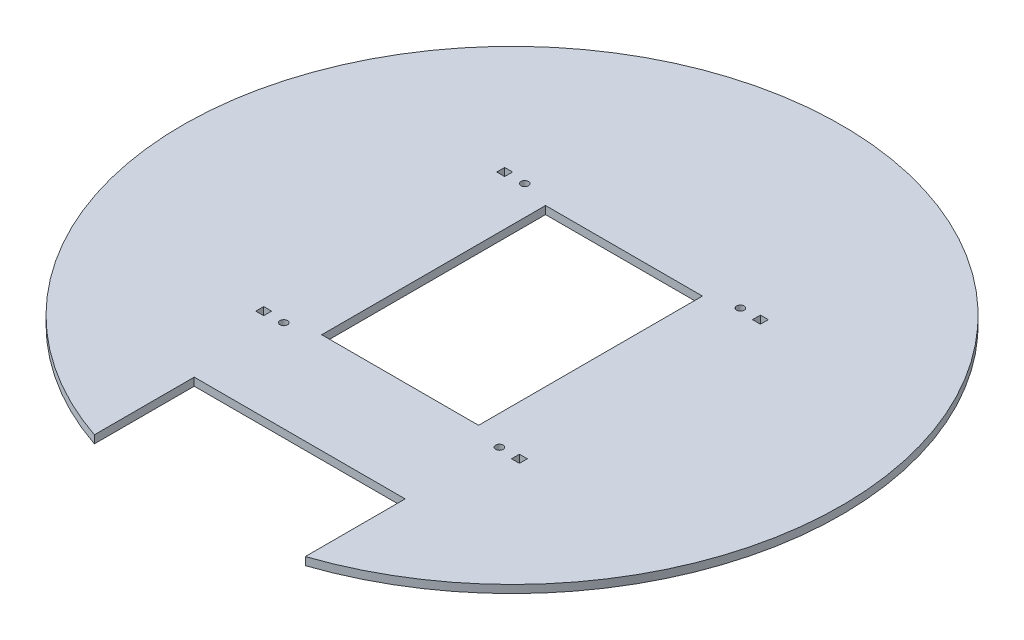
SolidWorks part; units mm, degrees
material "Acrylic (Medium-high impact)"
ref_plane "Front Plane" through (0, 0, 0) normal (0, 0, 1) x (1, 0, 0)
ref_plane "Top Plane" through (0, 0, 0) normal (0, 1, 0) x (1, 0, 0)
ref_plane "Right Plane" through (0, 0, 0) normal (1, 0, 0) x (0, 0, -1)
sketch "Sketch1" plane through (0, 0, 0) normal (0, 1, 0) x (1, 0, 0)
  line L0 (-29.75, -42.45) -> (-29.75, 42.45)
  line L1 (-31.75, -44.45) -> (31.75, -44.45) construction
  line L2 (-31.75, -44.45) -> (-31.75, 44.45) construction
  line L3 (-31.75, 44.45) -> (31.75, 44.45) construction
  line L4 (31.75, -44.45) -> (31.75, 44.45) construction
  line L5 (-31.75, -44.45) -> (31.75, 44.45) construction
  line L6 (-31.75, 44.45) -> (31.75, -44.45) construction
  line L7 (-29.75, 42.45) -> (29.75, 42.45)
  line L8 (29.75, -42.45) -> (29.75, 42.45)
  line L9 (-29.75, -42.45) -> (29.75, -42.45)
  circle A0 centre (0, 0) radius 125
  point P0 (0, 0)
  dimension "D3" = 250
  dimension "D1" = 63.5
  dimension "D2" = 88.9
  dimension "D4" = 2
extrude "Boss-Extrude1" add sketch "Sketch1" along normal blind 3
sketch "Sketch3" plane through (0, 3, 0) normal (0, 1, 0) x (1, 0, 0)
  line L0 (-42.4, 47.2) -> (-39.4, 44.2) construction
  line L1 (42.4, 47.2) -> (39.4, 44.2) construction
  line L2 (0, 0) -> (25.2091, 0) construction
  line L7 (-50, 44.2) -> (-47, 44.2)
  line L8 (-47, 44.2) -> (-47, 47.2)
  line L9 (-47, 47.2) -> (-50, 47.2)
  line L10 (-50, 47.2) -> (-50, 44.2)
  line L11 (-50, 44.2) -> (-47, 44.2)
  line L12 (-47, 44.2) -> (-47, 47.2)
  line L13 (-47, 47.2) -> (-50, 47.2)
  line L14 (-50, 47.2) -> (-50, 44.2)
  line L15 (47, 44.2) -> (50, 44.2)
  line L16 (50, 44.2) -> (50, 47.2)
  line L17 (50, 47.2) -> (47, 47.2)
  line L18 (47, 47.2) -> (47, 44.2)
  line L19 (47, 44.2) -> (50, 44.2)
  line L20 (50, 44.2) -> (50, 47.2)
  line L21 (50, 47.2) -> (47, 47.2)
  line L22 (47, 47.2) -> (47, 44.2)
  line L23 (47, -47.2) -> (50, -47.2) construction
  line L24 (50, -47.2) -> (50, -44.2) construction
  line L25 (50, -44.2) -> (47, -44.2) construction
  line L26 (47, -44.2) -> (47, -47.2) construction
  line L31 (-50, -47.2) -> (-47, -47.2) construction
  line L32 (-47, -47.2) -> (-47, -44.2) construction
  line L33 (-47, -44.2) -> (-50, -44.2) construction
  line L34 (-50, -44.2) -> (-50, -47.2) construction
  line L51 (47, -47.2) -> (50, -47.2)
  line L52 (50, -47.2) -> (50, -44.2)
  line L53 (50, -44.2) -> (47, -44.2)
  line L54 (47, -44.2) -> (47, -47.2)
  line L55 (-50, -47.2) -> (-47, -47.2)
  line L56 (-47, -47.2) -> (-47, -44.2)
  line L57 (-47, -44.2) -> (-50, -44.2)
  line L58 (-50, -44.2) -> (-50, -47.2)
  circle A0 centre (-40.9, 45.7) radius 1.4224
  circle A1 centre (40.9, 45.7) radius 1.4224
  circle A2 centre (40.9, -45.7) radius 1.4224
  circle A3 centre (-40.9, -45.7) radius 1.4224
  point P33 (0, 0)
  dimension "D1" = 2.8448
  dimension "D2" = 0
  dimension "D3" = 0
extrude "Cut-Extrude1" cut sketch "Sketch3" against normal blind 10
sketch "Sketch4" plane through (0, 3, 0) normal (0, 1, 0) x (1, 0, 0)
  line L1 (-52.6396, -60.6627) -> (52.6396, -60.6627)
  line L2 (-52.6396, -60.6627) -> (-52.6396, 60.6627)
  line L3 (-52.6396, 60.6627) -> (52.6396, 60.6627)
  line L4 (52.6396, -60.6627) -> (52.6396, 60.6627)
  line L5 (-52.6396, -60.6627) -> (52.6396, 60.6627) construction
  line L6 (-52.6396, 60.6627) -> (52.6396, -60.6627) construction
  line L7 (-176.3133, 139.7199) -> (176.3133, 139.7199)
  line L8 (-176.3133, 139.7199) -> (-176.3133, -139.7199)
  line L9 (-176.3133, -139.7199) -> (176.3133, -139.7199)
  line L10 (176.3133, 139.7199) -> (176.3133, -139.7199)
  line L11 (-176.3133, 139.7199) -> (176.3133, -139.7199) construction
  line L12 (-176.3133, -139.7199) -> (176.3133, 139.7199) construction
  point P0 (0, 0)
  point P6 (0, 0)
extrude "Cut-Extrude2" [suppressed] cut sketch "Sketch4" against normal blind 10
sketch "Sketch6" plane through (0, 3, 0) normal (0, 1, 0) x (1, 0, 0)
  line L0 (-29.75, -42.45) -> (29.75, -42.45) construction
  line L1 (-40, -80.55) -> (40, -80.55)
  line L2 (-40, -80.55) -> (-40, -142.0913)
  line L3 (-40, -142.0913) -> (40, -142.0913)
  line L4 (40, -80.55) -> (40, -142.0913)
  line L5 (-40, -80.55) -> (40, -142.0913) construction
  line L6 (-40, -142.0913) -> (40, -80.55) construction
  point P0 (0, -111.3206)
  point P5 (0, 0)
  dimension "D1" = 38.1
  dimension "D2" = 80
extrude "Cut-Extrude3" cut sketch "Sketch6" against normal blind 3
